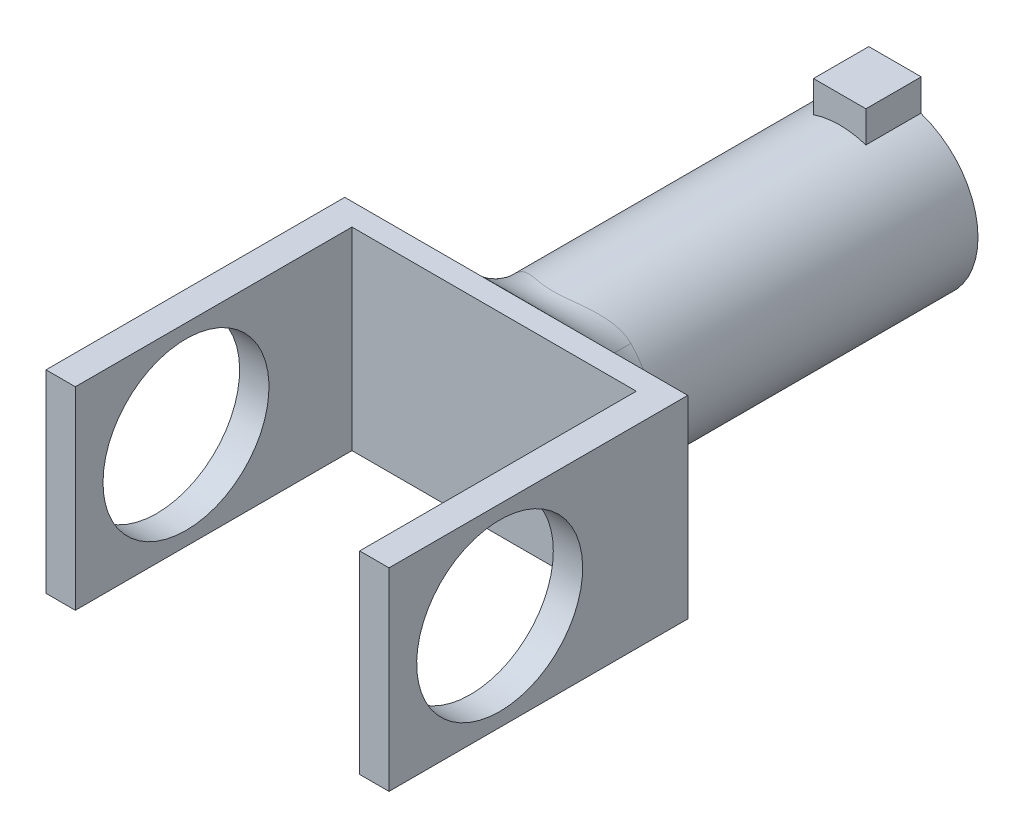
SolidWorks part; units mm, degrees
ref_plane "Front Plane" through (0, 0, 0) normal (0, 0, 1) x (1, 0, 0)
ref_plane "Top Plane" through (0, 0, 0) normal (0, 1, 0) x (1, 0, 0)
ref_plane "Right Plane" through (0, 0, 0) normal (1, 0, 0) x (0, 0, -1)
sketch "Sketch1" plane through (0, 0, 0) normal (0, 0, 1) x (1, 0, 0)
  circle A0 centre (0, 0) radius 15
  dimension "D1" = 30
extrude "Boss-Extrude1" add sketch "Sketch1" along normal mid plane 68.46
sketch "Sketch2" plane through (0, 0, 34.23) normal (0, 0, 1) x (1, 0, 0)
  line L1 (-31, 17.5) -> (31, 17.5)
  line L2 (-31, 17.5) -> (-31, -17.5)
  line L3 (-31, -17.5) -> (31, -17.5)
  line L4 (31, 17.5) -> (31, -17.5)
  line L5 (-31, 17.5) -> (31, -17.5) construction
  line L6 (-31, -17.5) -> (31, 17.5) construction
  point P0 (0, 0)
  dimension "D1" = 35
  dimension "D2" = 62
extrude "Boss-Extrude2" add sketch "Sketch2" along normal blind 4
fillet "Fillet1" radius 10 1 edges at (15, 0, 34.23)
sketch "Sketch3" plane through (0, 0, 38.23) normal (0, 0, 1) x (1, 0, 0)
  line L0 (-31, -17.5) -> (31, -17.5) construction
  line L1 (-31, 17.5) -> (-25.6973, 17.5)
  line L2 (-31, 17.5) -> (-31, -17.5)
  line L3 (-31, -17.5) -> (-25.6973, -17.5)
  line L4 (-25.6973, 17.5) -> (-25.6973, -17.5)
  line L5 (0, -1000) -> (0, 49000) construction
  line L6 (25.6973, 17.5) -> (25.6973, -17.5)
  line L7 (31, -17.5) -> (25.6973, -17.5)
  line L8 (31, 17.5) -> (31, -17.5)
  line L9 (31, 17.5) -> (25.6973, 17.5)
extrude "Boss-Extrude3" add sketch "Sketch3" along normal blind 50
sketch "Sketch5" plane through (-31, 0, 0) normal (-1, 0, 0) x (0, 0, 1)
  line L0 (68.23, -999.1746) -> (68.23, 49000.8254) construction
  line L1 (88.23, 17.5) -> (88.23, -17.5) construction
  line L2 (18.23, -1002.6574) -> (18.23, 48997.3426) construction
  line L3 (-862, 0) -> (49138, 0) construction
  circle A0 centre (68.23, 0) radius 15
  point P9 (88.23, 0)
  dimension "D1" = 20
  dimension "D2" = 50
extrude "Cut-Extrude1" cut sketch "Sketch5" against normal blind 112
sketch "Sketch8" plane through (0, 0, -34.23) normal (0, 0, -1) x (-1, 0, 0)
  line L0 (-4.7406, 20) -> (-4.7406, 14.3352)
  line L1 (-4.7406, 20) -> (4.7406, 20)
  line L3 (4.7406, 20) -> (4.7406, 14.3352)
  arc A0 (-4.7406, 14.3352) -> (4.7406, 14.3352) centre (0, 0) cw
extrude "Boss-Extrude4" add sketch "Sketch8" against normal blind 10 separate body
